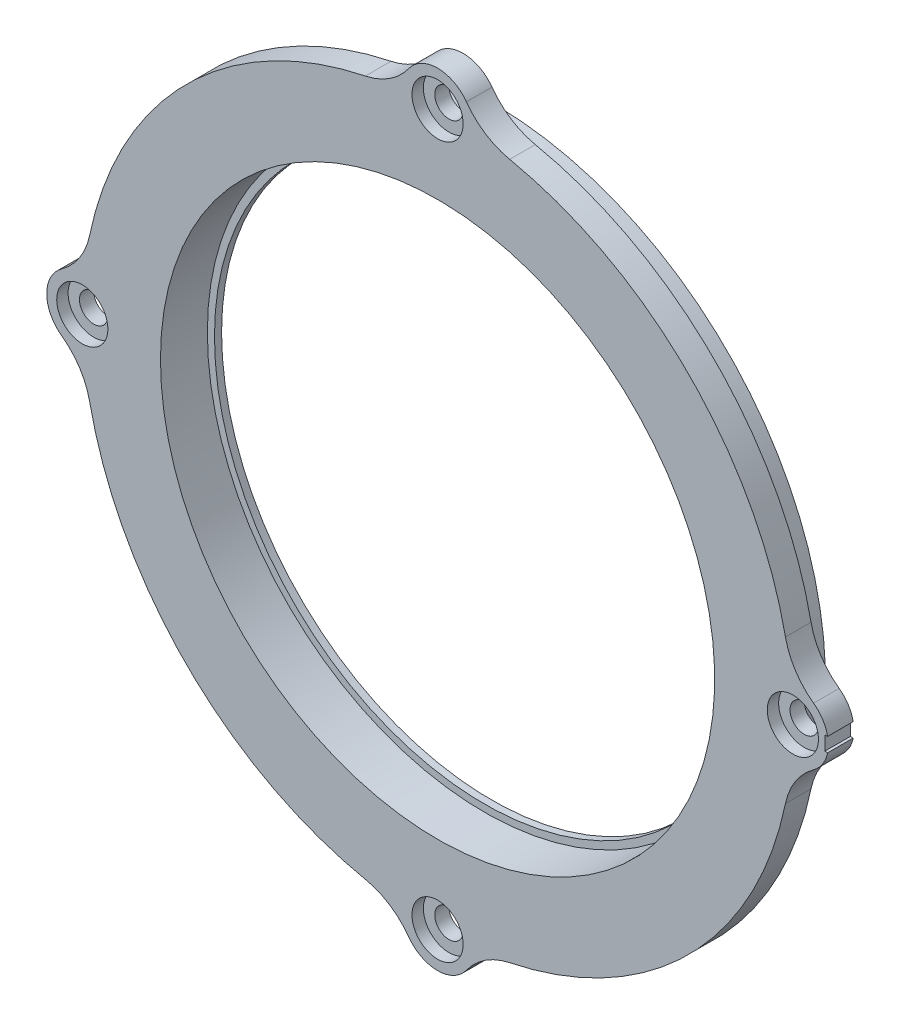
SolidWorks part; units mm, degrees
material "PET"
ref_plane "Front Plane" through (0, 0, 0) normal (0, 0, 1) x (1, 0, 0)
ref_plane "Top Plane" through (0, 0, 0) normal (0, 1, 0) x (1, 0, 0)
ref_plane "Right Plane" through (0, 0, 0) normal (1, 0, 0) x (0, 0, -1)
sketch "Sketch2" plane through (0, 0, 0) normal (0, 0, 1) x (1, 0, 0)
  circle A3 centre (0, 0) radius 50
  circle A4 centre (0, 0) radius 39
  dimension "D2" = 78
  dimension "D1" = 100
extrude "Boss-Extrude1" add sketch "Sketch2" along normal blind 5
sketch "Sketch3" plane through (0, 0, 0) normal (0, 0, -1) x (-1, 0, 0)
  circle A0 centre (-43, 0) radius 3
  circle A1 centre (0, 0) radius 39
  circle A2 centre (0, 0) radius 47
  circle A3 centre (0, 0) radius 50 construction
  circle A4 centre (-32.9399, 27.6399) radius 3
  circle A5 centre (-7.4669, 42.3467) radius 3
  circle A6 centre (21.5, 37.2391) radius 3
  circle A7 centre (40.4068, 14.7069) radius 3
  circle A8 centre (40.4068, -14.7069) radius 3
  circle A9 centre (21.5, -37.2391) radius 3
  circle A10 centre (-7.4669, -42.3467) radius 3
  circle A11 centre (-32.9399, -27.6399) radius 3
  point P27 (0, 0)
  dimension "D1" = 43
  dimension "D2" = 6
  dimension "D3" = 3
  dimension "D4" = 9
extrude "Boss-Extrude2" add sketch "Sketch3" along normal blind 4
sketch "Sketch4" plane through (0, 0, -4) normal (0, 0, -1) x (-1, 0, 0)
  circle A0 centre (0, 0) radius 39
  circle A1 centre (0, 0) radius 38
  dimension "D1" = 1
extrude "Boss-Extrude3" add sketch "Sketch4" against normal blind 1
sketch "Sketch6" plane through (0, 0, 5) normal (0, 0, 1) x (1, 0, 0)
  line L0 (0, 0) -> (50, 0) construction
  line L1 (0, 0) -> (0, 50) construction
  circle A0 centre (50, 0) radius 2
  circle A1 centre (50, 0) radius 5
  circle A2 centre (-50, 0) radius 5
  circle A3 centre (-50, 0) radius 2
  circle A4 centre (0, 50) radius 5
  circle A5 centre (0, 50) radius 2
  circle A8 centre (0, -50) radius 2
  circle A9 centre (0, -50) radius 5
  circle M6 centre (0, 0) radius 50
  dimension "D1" = 4
  dimension "D4" = 10
  dimension "D5" = 4
  dimension "D3" = 50
  dimension "D6" = 50
  dimension "D2" = 3
extrude "Boss-Extrude4" add sketch "Sketch6" against normal up to surface (5 mm away) up to face at (-47, 0, 0)
fillet "Fillet1" radius 10 8 edges at (49.75, 4.9937, 2.5) (4.9937, 49.75, 2.5) (-4.9937, 49.75, 2.5) (-49.75, 4.9937, 2.5) (-49.75, -4.9937, 2.5) (49.75, -4.9937, 2.5) (4.9937, -49.75, 2.5) (-4.9937, -49.75, 2.5)
sketch "Sketch7" plane through (0, 0, 5) normal (0, 0, 1) x (1, 0, 0)
  circle A0 centre (50, 0) radius 3.6
  circle A1 centre (0, 50) radius 3.6
  circle A2 centre (-50, 0) radius 3.6
  circle A3 centre (0, -50) radius 3.6
  dimension "D1" = 7.2
  dimension "D2" = 7.2
  dimension "D3" = 7.2
  dimension "D4" = 7.2
extrude "Cut-Extrude1" cut sketch "Sketch7" against normal blind 3
sketch "Sketch8" plane through (0, 0, -4) normal (0, 0, -1) x (-1, 0, 0)
  circle A1 centre (-32.9399, 27.6399) radius 3.15
  circle A2 centre (-43, 0) radius 3.15
  circle A3 centre (-43, 0) radius 3.15
  circle A4 centre (-7.4669, 42.3467) radius 3.15
  circle A5 centre (21.5, 37.2391) radius 3.15
  circle A6 centre (40.4068, 14.7069) radius 3.15
  circle A7 centre (40.4068, -14.7069) radius 3.15
  circle A8 centre (21.5, -37.2391) radius 3.15
  circle A9 centre (-7.4669, -42.3467) radius 3.15
  circle A10 centre (-32.9399, -27.6399) radius 3.15
  point P22 (0, 0)
  dimension "D1" = 0.15
  dimension "D2" = 9
extrude "Cut-Extrude2" cut sketch "Sketch8" against normal blind 6.6
sketch "Sketch10" plane through (0, 0, 0) normal (0, 1, 0) x (1, 0, 0)
  line L0 (-55, 0) -> (-55, -5) construction
  line L1 (-55, -3.6) -> (57, -3.6)
  line L2 (-55, -3.6) -> (-55, -5)
  line L3 (-55, -5) -> (57, -5)
  line L4 (57, -3.6) -> (57, -5)
  line L5 (52.9167, -5) -> (55, -5) construction
  dimension "D1" = 1.4
extrude "Cut-Extrude4" cut sketch "Sketch10" against normal mid plane 131.6
extrude "Cut-Extrude5" cut sketch "Sketch6<5>" against normal blind 10 contours A3 M6 | A5 M6 | A0 M6 | A8 M6 region at (49.144, 0, 5) region at (0, 49.144, 5) region at (0, -49.144, 5) region at (-49.144, 0, 5)
sketch "Sketch6<5>" plane through (0, 0, 5) normal (0, 0, 1) x (1, 0, 0) same geometry as "Sketch6"
sketch "Sketch11" plane through (0, 0, -4) normal (0, 0, -1) x (-1, 0, 0)
  line L0 (0, 0) -> (-65.6734, 0) construction
  line L2 (-55.5, -1) -> (-54.5, -1)
  line L3 (-55.5, -1) -> (-55.5, 1)
  line L4 (-55.5, 1) -> (-54.5, 1)
  line L5 (-54.5, -1) -> (-54.5, 1)
  line L6 (-55.5, -1) -> (-54.5, 1) construction
  line L7 (-55.5, 1) -> (-54.5, -1) construction
  arc A0 (-52.9167, 4.0612) -> (-52.9167, -4.0612) centre (-50, 0) ccw construction
  point P3 (-55, 0)
  dimension "D1" = 2
  dimension "D2" = 1
extrude "Cut-Extrude6" cut sketch "Sketch11" against normal blind 12
sketch "Sketch13" plane through (0, 0, 2.6) normal (0, 0, -1) x (-1, 0, 0)
  circle A1 centre (-32.9399, 27.6399) radius 3.15
  circle A2 centre (-43, 0) radius 3.15
  circle A3 centre (-43, 0) radius 3.15
  circle A4 centre (-7.4669, 42.3467) radius 3.15
  circle A5 centre (21.5, 37.2391) radius 3.15
  circle A6 centre (40.4068, 14.7069) radius 3.15
  circle A7 centre (40.4068, -14.7069) radius 3.15
  circle A8 centre (21.5, -37.2391) radius 3.15
  circle A9 centre (-7.4669, -42.3467) radius 3.15
  circle A10 centre (-32.9399, -27.6399) radius 3.15
  point P22 (0, 0)
  dimension "D1" = 0
  dimension "D2" = 9
extrude "Boss-Extrude6" add sketch "Sketch13" along normal blind 0.7
